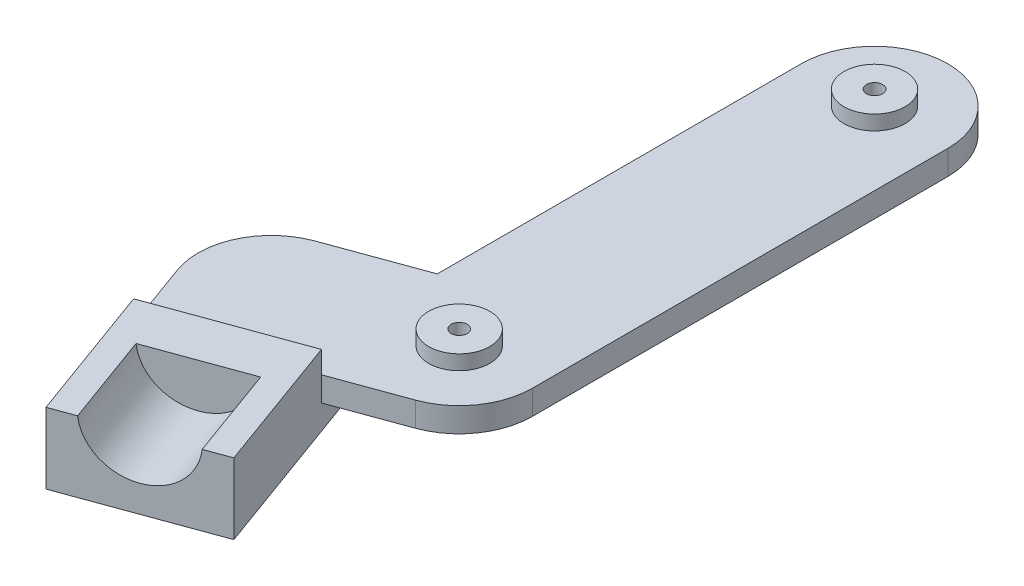
SolidWorks part; units mm, degrees
material "7075-T6 (SN)"
ref_plane "정면" through (0, 0, 0) normal (0, 0, 1) x (1, 0, 0)
ref_plane "윗면" through (0, 0, 0) normal (0, 1, 0) x (1, 0, 0)
ref_plane "우측면" through (0, 0, 0) normal (1, 0, 0) x (0, 0, -1)
sketch "스케치1" plane through (0, 0, 0) normal (0, 1, 0) x (1, 0, 0)
  line L0 (0, 0) -> (0, 85) construction
  line L2 (-15, 0) -> (-15, 85)
  line L3 (15, 0) -> (15, 85)
  arc A0 (-15, 0) -> (15, 0) centre (0, 0) ccw
  arc A1 (15, 85) -> (-15, 85) centre (0, 85) ccw
  point P5 (0, 42.5)
  dimension "D2" = 15
  dimension "D1" = 85
extrude "보스-돌출1" add sketch "스케치1" along normal blind 5
sketch "스케치2" plane through (0, 5, 0) normal (0, 1, 0) x (1, 0, 0)
  line L0 (0, 85) -> (0, 0) construction
  circle A0 centre (0, 85) radius 6.25
  circle A1 centre (0, 0) radius 6.25
  dimension "D2" = 12.5
  dimension "D3" = 12.5
  dimension "D1" = 85
extrude "보스-돌출2" add sketch "스케치2" along normal blind 3
hole_wizard "M4 탭을 위한 탭 드릴1" positions "스케치5" profile "스케치7" hole size "M4" standard "ISO"
sketch "스케치5" plane through (0, 8, 0) normal (0, 1, 0) x (1, 0, 0)
  point P0 (0, 0)
  point P3 (0, 85)
sketch "스케치7" plane through (0, 8, 0) normal (1, 0, 0) x (0, 0, 1)
  line L0 (0, 0) -> (0, 5.9914)
  line L1 (0, 5.9914) -> (1.65, 5)
  line L2 (1.65, 5) -> (1.65, 0)
  line L5 (1.65, 0) -> (0, 0)
  line L10 (0, 5.9914) -> (-1.65, 5) construction
  line L11 (0, -6.35) -> (0, 107.95) construction
  dimension "구멍 지름" = 3.3
  dimension "구멍 깊이" = 5
  dimension "드릴 각도" = 118
sketch "스케치9" plane through (0, 0, 0) normal (0, -1, 0) x (1, 0, 0)
  line L0 (0, 0) -> (-41.3824, 15.062) construction
  line L1 (-15, -85) -> (-15, 0) construction
  line L2 (0, 0) -> (-28.1908, 10.2606) construction
  line L3 (-5.1303, -14.0954) -> (-33.3211, -3.8348)
  line L4 (5.1303, 14.0954) -> (-23.0605, 24.356)
  arc A0 (-5.1303, -14.0954) -> (5.1303, 14.0954) centre (0, 0) ccw
  arc A1 (-23.0605, 24.356) -> (-33.3211, -3.8348) centre (-28.1908, 10.2606) ccw
  point P5 (-14.0954, 5.1303)
  dimension "D3" = 15
  dimension "D1" = 110
  dimension "D2" = 30
extrude "보스-돌출3" add sketch "스케치9" against normal blind 5
sketch "스케치10" plane through (0, 0, 0) normal (0, -1, 0) x (1, 0, 0)
  line L0 (-28.1908, 10.2606) -> (0, 0) construction
  line L3 (-42.2862, 15.3909) -> (-26.8953, 57.6771)
  line L6 (-28.1908, 10.2606) -> (-14.9216, 46.7173) construction
  line L7 (-14.0954, 5.1303) -> (1.2955, 47.4165)
  line L8 (-26.8953, 57.6771) -> (1.2955, 47.4165)
  arc A4 (-42.2862, 15.3909) -> (-14.0954, 5.1303) centre (-28.1908, 10.2606) ccw
  dimension "D2" = 90
  dimension "D3" = 45
  dimension "D1" = 30
extrude "보스-돌출4" add sketch "스케치10" against normal blind 5 and the other way blind 5
sketch "스케치11" plane through (0, 5, 0) normal (0, 1, 0) x (1, 0, 0)
  line L0 (-26.8953, -57.6771) -> (-42.2862, -15.3909) construction
  line L1 (1.2955, -47.4165) -> (-26.8953, -57.6771) construction
  line L2 (-8.9651, -19.2257) -> (1.2955, -47.4165) construction
  line L3 (-26.8953, -57.6771) -> (-37.1559, -29.4863)
  line L4 (1.2955, -47.4165) -> (-26.8953, -57.6771)
  line L5 (-8.9651, -19.2257) -> (1.2955, -47.4165)
  line L6 (-8.9651, -19.2257) -> (-37.1559, -29.4863)
extrude "보스-돌출5" add sketch "스케치11" along normal blind 4.5
sketch "스케치12" plane through (15.3909, 0, 42.2862) normal (0.342, 0, 0.9397) x (0.9397, 0, -0.342)
  line L0 (-45, 9.5) -> (-15, 9.5) construction
  line L1 (-48.0608, 10.5) -> (-11.833, 10.5) construction
  line L2 (-45, -5) -> (-45, 9.5) construction
  circle A0 centre (-30, 10.5) radius 10
  point P6 (0, 0)
  point P7 (0, 0)
  point P12 (0, 0)
  point P13 (0, 0)
  dimension "D1" = 20
  dimension "D2" = 1
  dimension "D3" = 15
extrude "컷-돌출1" cut sketch "스케치12" against normal blind 20
